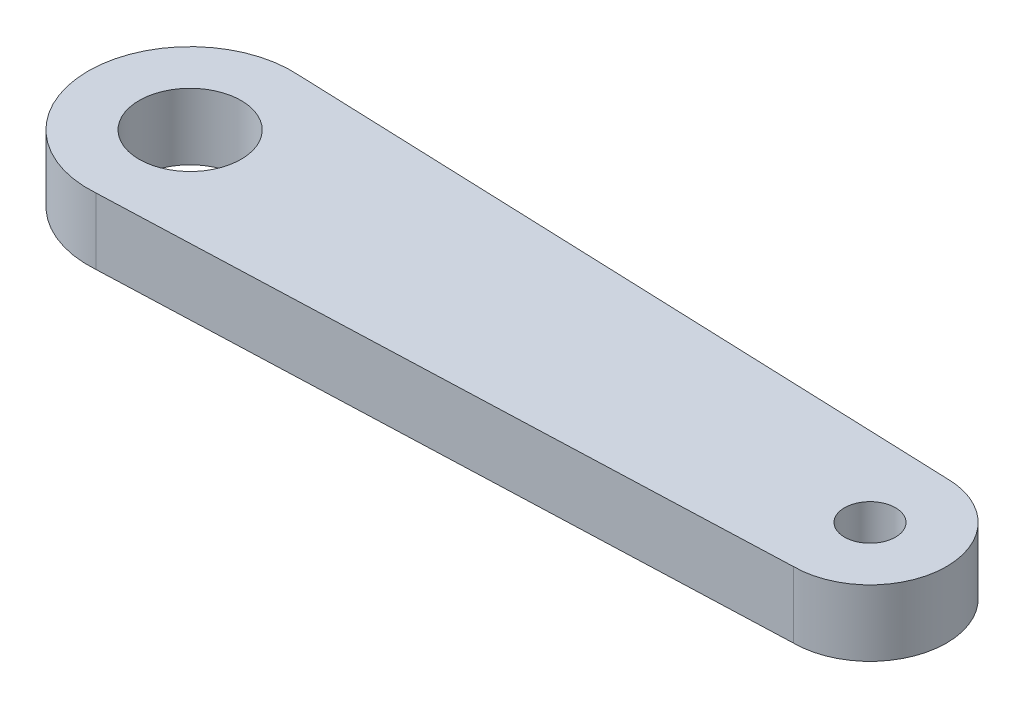
SolidWorks part; units mm, degrees
ref_plane "Front Plane" through (0, 0, 0) normal (0, 0, 1) x (1, 0, 0)
ref_plane "Top Plane" through (0, 0, 0) normal (0, 1, 0) x (1, 0, 0)
ref_plane "Right Plane" through (0, 0, 0) normal (1, 0, 0) x (0, 0, -1)
sketch "Sketch1" plane through (0, 0, 0) normal (0, 1, 0) x (1, 0, 0)
  line L0 (0.4494, 5.9831) -> (40, 4.5)
  line L1 (0.4494, -5.9831) -> (40, -4.5)
  arc A0 (0.4494, 5.9831) -> (0.4494, -5.9831) centre (0, 0) ccw
  arc A1 (40, -4.5) -> (40, 4.5) centre (40, 0) ccw
  dimension "D2" = 6
  dimension "D3" = 4.5
  dimension "D1" = 40
extrude "Boss-Extrude1" add sketch "Sketch1" along normal blind 3.9 contours L1 A1 L0 A0
sketch "Sketch2" plane through (0, 3.9, 0) normal (0, 1, 0) x (1, 0, 0)
  circle A0 centre (0, 0) radius 3
  circle A1 centre (40, 0) radius 1.5
  dimension "D1" = 6
  dimension "D2" = 3
extrude "Cut-Extrude1" cut sketch "Sketch2" against normal blind 10.5 and the other way blind 16
